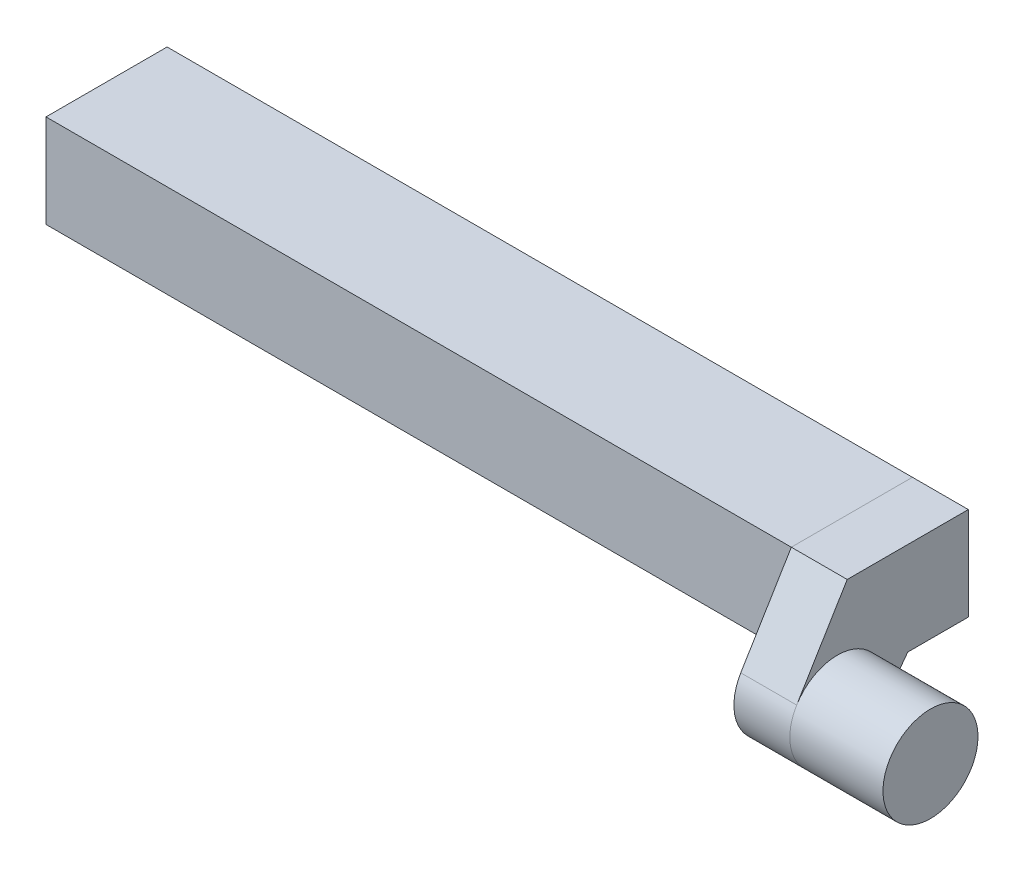
SolidWorks part; units mm, degrees
ref_plane "Front Plane" through (0, 0, 0) normal (0, 0, 1) x (1, 0, 0)
ref_plane "Top Plane" through (0, 0, 0) normal (0, 1, 0) x (1, 0, 0)
ref_plane "Right Plane" through (0, 0, 0) normal (1, 0, 0) x (0, 0, -1)
sketch "Sketch2" plane through (0, 0, 0) normal (1, 0, 0) x (0, 0, -1)
  line L1 (-2.05, -2.05) -> (2.05, -2.05)
  line L2 (-2.05, -2.05) -> (-2.05, 2.05)
  line L3 (-2.05, 2.05) -> (2.05, 2.05)
  line L4 (2.05, -2.05) -> (2.05, 2.05)
  line L5 (-2.05, -2.05) -> (2.05, 2.05) construction
  line L6 (-2.05, 2.05) -> (2.05, -2.05) construction
  line L7 (3.25, -2.5) -> (-3.25, -2.5)
  line L8 (3.25, -2.5) -> (3.25, 2.5)
  line L9 (3.25, 2.5) -> (-3.25, 2.5)
  line L10 (-3.25, -2.5) -> (-3.25, 2.5)
  line L11 (3.25, -2.5) -> (-3.25, 2.5) construction
  line L12 (3.25, 2.5) -> (-3.25, -2.5) construction
  point P0 (0, 0)
  point P5 (0, 0)
  dimension "D1" = 4.1
  dimension "D2" = 4.1
  dimension "D3" = 6.5
  dimension "D4" = 5
extrude "Boss-Extrude1" add sketch "Sketch2" along normal blind 10
extrude "Boss-Extrude2" add sketch "Sketch2<2>" along normal blind 25 from offset 15 contours L1 L4 L3 L2 | L10 L7 L8 L9 L4 L1 L2 L3 region at (0, 0, 0) region at (0, -2.418, 0)
sketch "Sketch2<2>" plane through (0, 0, 0) normal (1, 0, 0) x (0, 0, -1) same geometry as "Sketch2"
sketch "Sketch5" plane through (40, 0, 0) normal (1, 0, 0) x (0, 0, -1)
  line L0 (-0.02, -0.4959) -> (-4.75, -0.4959) construction
  line L5 (-5.9623, -1.983) -> (-3.25, 2.5)
  line L6 (-3.25, 2.5) -> (3.25, 2.5)
  line L7 (3.25, 2.5) -> (3.25, -2.5)
  line L8 (3.25, -2.5) -> (0, -2.5)
  line L9 (-3.25, -2.5) -> (3.25, -2.5) construction
  line L10 (0, -2.5) -> (-1.7367, -4.8278)
  arc A1 (-5.9623, -1.983) -> (-1.7367, -4.8278) centre (-3.7806, -3.303) ccw
  dimension "D2" = 2.55
  dimension "D1" = 4.73
  dimension "D3" = 5
extrude "Boss-Extrude3" add sketch "Sketch5" along normal blind 3
sketch "Sketch6" plane through (43, 0, 0) normal (1, 0, 0) x (0, 0, -1)
  circle A1 centre (-3.7806, -3.303) radius 2.55
  dimension "D1" = 5.1
extrude "Boss-Extrude4" add sketch "Sketch6" along normal blind 5
extrude "Boss-Extrude5" add sketch "Sketch2<4>" along normal blind 5 from offset 10
sketch "Sketch2<4>" plane through (0, 0, 0) normal (1, 0, 0) x (0, 0, -1) same geometry as "Sketch2"
